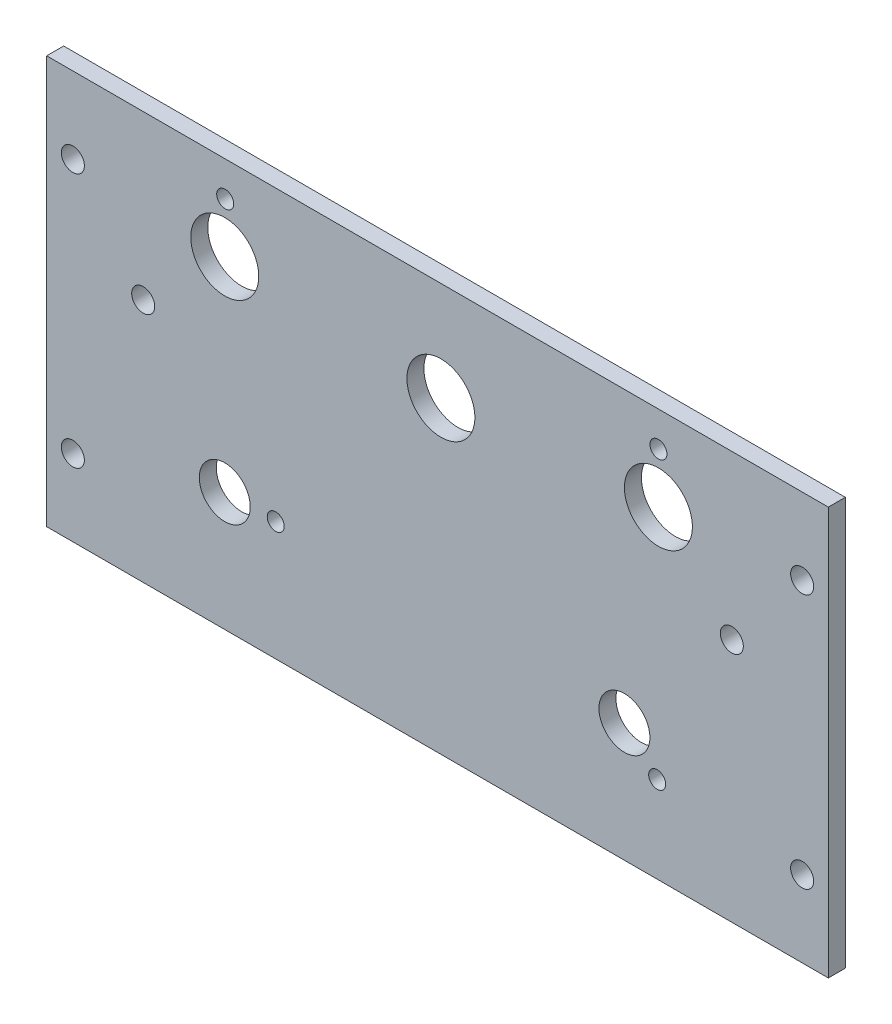
SolidWorks part; units mm, degrees
ref_plane "Front Plane" through (0, 0, 0) normal (0, 0, 1) x (1, 0, 0)
ref_plane "Top Plane" through (0, 0, 0) normal (0, 1, 0) x (1, 0, 0)
ref_plane "Right Plane" through (0, 0, 0) normal (1, 0, 0) x (0, 0, -1)
sketch "Sketch1" plane through (0, 0, 0) normal (0, 0, 1) x (1, 0, 0)
  line L4 (0, 76.2) -> (-146.05, 76.2)
  line L5 (-146.05, 76.2) -> (-146.05, 0)
  line L6 (-146.05, 0) -> (0, 0)
  line L7 (0, 0) -> (0, 76.2)
  line L8 (0, 76.2) -> (-146.05, 76.2)
  line L9 (-146.05, 76.2) -> (-146.05, 0)
  line L10 (-146.05, 0) -> (0, 0)
  line L11 (0, 0) -> (0, 76.2)
  dimension "D1" = 0
extrude "Boss-Extrude1" add sketch "Sketch1" against normal blind 3.175
hole_wizard "#6 Clearance Hole1" positions "Sketch3" profile "Sketch2" hole size "#6" standard "ANSI Inch" end condition through all
sketch "Sketch3" plane through (0, 0, -3.175) normal (0, 0, -1) x (-1, 0, 0)
  point P0 (4.8895, 61.9125)
  point P3 (4.8895, 14.2875)
  point P6 (141.1605, 14.2875)
  point P9 (141.1605, 61.9125)
  point P12 (128.016, 45.72)
  point P15 (18.034, 45.72)
sketch "Sketch2" plane through (-4.8895, 61.9125, -3.175) normal (1, 0, 0) x (0, 1, 0)
  line L0 (0, 0) -> (0, 3.175)
  line L1 (0, 3.175) -> (2.1526, 3.175)
  line L2 (2.1526, 3.175) -> (2.1526, 0)
  line L5 (2.1526, 0) -> (0, 0)
  line L11 (0, -6.35) -> (0, 107.95) construction
  dimension "Thru Hole Dia." = 4.3053
  dimension "Thru Hole Depth" = 3.175
hole_wizard "1/2 (0.5) Diameter Hole1" positions "Sketch5" profile "Sketch4" hole size "1/2" standard "ANSI Inch" end condition through all
sketch "Sketch5" plane through (0, 0, -3.175) normal (0, 0, -1) x (-1, 0, 0)
  point P0 (31.75, 60.325)
  point P3 (72.39, 57.658)
  point P6 (112.776, 60.325)
sketch "Sketch4" plane through (-31.75, 60.325, -3.175) normal (1, 0, 0) x (0, 1, 0)
  line L0 (0, 0) -> (0, 3.175)
  line L1 (0, 3.175) -> (6.35, 3.175)
  line L2 (6.35, 3.175) -> (6.35, 0)
  line L5 (6.35, 0) -> (0, 0)
  line L11 (0, -6.35) -> (0, 107.95) construction
  dimension "Thru Hole Dia." = 12.7
  dimension "Thru Hole Depth" = 3.175
hole_wizard "3/8 (0.375) Diameter Hole1" positions "Sketch7" profile "Sketch6" hole size "3/8" standard "ANSI Inch" end condition through all
sketch "Sketch7" plane through (0, 0, -3.175) normal (0, 0, -1) x (-1, 0, 0)
  point P0 (38.1, 22.225)
  point P3 (112.776, 22.225)
sketch "Sketch6" plane through (-38.1, 22.225, -3.175) normal (1, 0, 0) x (0, 1, 0)
  line L0 (0, 0) -> (0, 3.175)
  line L1 (0, 3.175) -> (4.7625, 3.175)
  line L2 (4.7625, 3.175) -> (4.7625, 0)
  line L5 (4.7625, 0) -> (0, 0)
  line L11 (0, -6.35) -> (0, 107.95) construction
  dimension "Thru Hole Dia." = 9.525
  dimension "Thru Hole Depth" = 3.175
hole_wizard "1/8 (0.125) Diameter Hole1" positions "Sketch9" profile "Sketch8" hole size "1/8" standard "ANSI Inch" end condition through all
sketch "Sketch9" plane through (0, 0, -3.175) normal (0, 0, -1) x (-1, 0, 0)
  point P0 (31.75, 69.6995)
  point P2 (112.6954, 69.6995)
  point P4 (103.251, 22.225)
  point P6 (31.9807, 16.1303)
sketch "Sketch8" plane through (-31.75, 69.6995, -3.175) normal (1, 0, 0) x (0, 1, 0)
  line L0 (0, 0) -> (0, 3.175)
  line L1 (0, 3.175) -> (1.5875, 3.175)
  line L2 (1.5875, 3.175) -> (1.5875, 0)
  line L5 (1.5875, 0) -> (0, 0)
  line L11 (0, -6.35) -> (0, 107.95) construction
  dimension "Thru Hole Dia." = 3.175
  dimension "Thru Hole Depth" = 3.175
